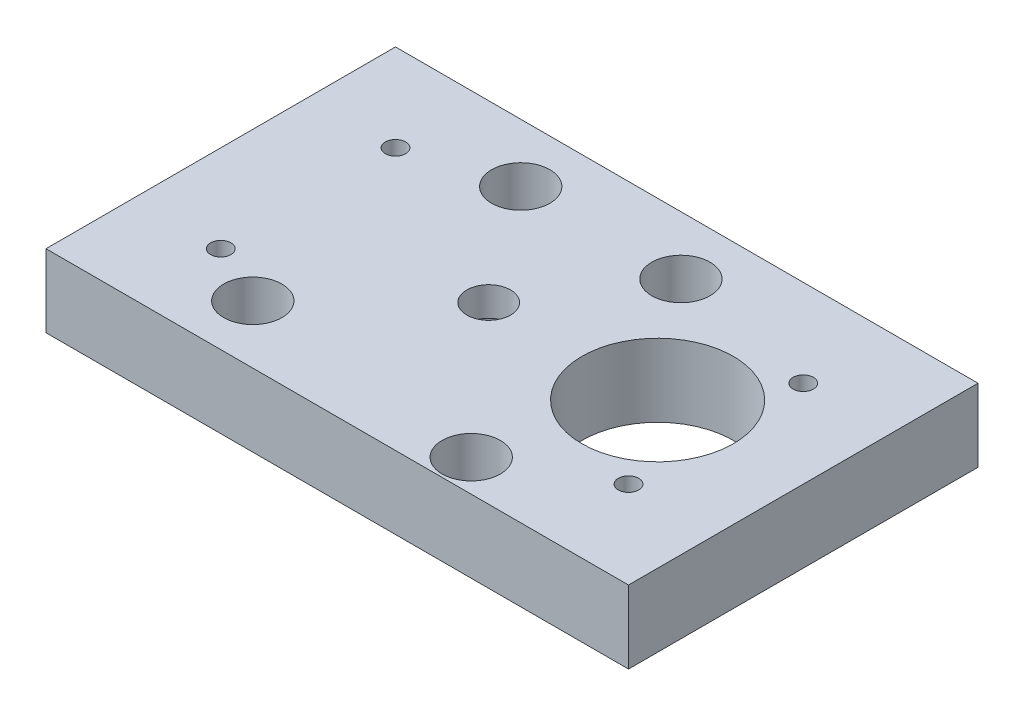
SolidWorks part; units mm, degrees
ref_plane "前视基准面" through (0, 0, 0) normal (0, 0, 1) x (1, 0, 0)
ref_plane "上视基准面" through (0, 0, 0) normal (0, 1, 0) x (1, 0, 0)
ref_plane "右视基准面" through (0, 0, 0) normal (1, 0, 0) x (0, 0, -1)
other "Configuration Table"
sketch "草图1" plane through (0, 0, 0) normal (0, 1, 0) x (1, 0, 0)
  line L0 (5.0509, -6) -> (27.896, -6) construction
  line L1 (0, 0) -> (20, 0)
  line L2 (0, 0) -> (0, -12)
  line L3 (0, -12) -> (20, -12)
  line L4 (20, 0) -> (20, -12)
  circle A3 centre (9.2, -6) radius 1.6
  circle A5 centre (15, -6) radius 2.6
  circle A6 centre (9.2, -6) radius 0.75
  point P5 (5, -6)
  dimension "D4" = 5.8
  dimension "D6" = 3.2
  dimension "D11" = 5.2
  dimension "D13" = 1.5
  dimension "D1" = 6
  dimension "D2" = 5
  dimension "D3" = 4.2
  dimension "D5" = 10
  dimension "D7" = 20
  dimension "D12" = 12
extrude "凸台-拉伸1" add sketch "草图1" along normal blind 2.5 contours L4 L3 L2 L1 | A3 | A5
extrude "凸台-拉伸2" add sketch "草图1<5>" against normal blind 1 from surface contours A3 | A6 starting at face at (10, 2.5, 6)
sketch "草图1<5>" plane through (0, 0, 0) normal (0, 1, 0) x (1, 0, 0) same geometry as "草图1"
sketch "草图3" plane through (0, 2.5, 0) normal (0, 1, 0) x (1, 0, 0)
  line L0 (0, 0) -> (0, -12) construction
  line L1 (0, 0) -> (20, 0) construction
  line L2 (0, -12) -> (20, -12) construction
  line L3 (20, 0) -> (20, -12) construction
  circle A0 centre (6.3, -2) radius 1
  circle A1 centre (5.1, -10) radius 1
  circle A2 centre (11.8, -2) radius 1
  circle A3 centre (13.5, -10.9) radius 1
  circle A4 centre (5.1, -10) radius 0.7
  circle A5 centre (6.3, -2) radius 0.7
  circle A6 centre (11.8, -2) radius 0.7
  circle A7 centre (13.5, -10.9) radius 0.7
  circle A11 centre (3, -3) radius 0.35
  circle A12 centre (3, -9) radius 0.35
  circle A13 centre (17, -9) radius 0.35
  circle A14 centre (17, -3) radius 0.35
  dimension "D1" = 1.4
  dimension "D2" = 2
  dimension "D3" = 0.7
  dimension "D4" = 3
  dimension "D5" = 3
  dimension "D6" = 3
  dimension "D7" = 3
  dimension "D8" = 3
  dimension "D9" = 3
  dimension "D10" = 3
  dimension "D11" = 3
extrude "切除-拉伸1" cut sketch "草图3" against normal through all contours A5 | A4 | A6 | A7 | A12 | A11 | A14 | A13
extrude "切除-拉伸2" cut sketch "草图3<3>" against normal blind 1.5 contours A0 | A1 | A3 | A2
sketch "草图3<3>" plane through (0, 2.5, 0) normal (0, 1, 0) x (1, 0, 0) same geometry as "草图3"
